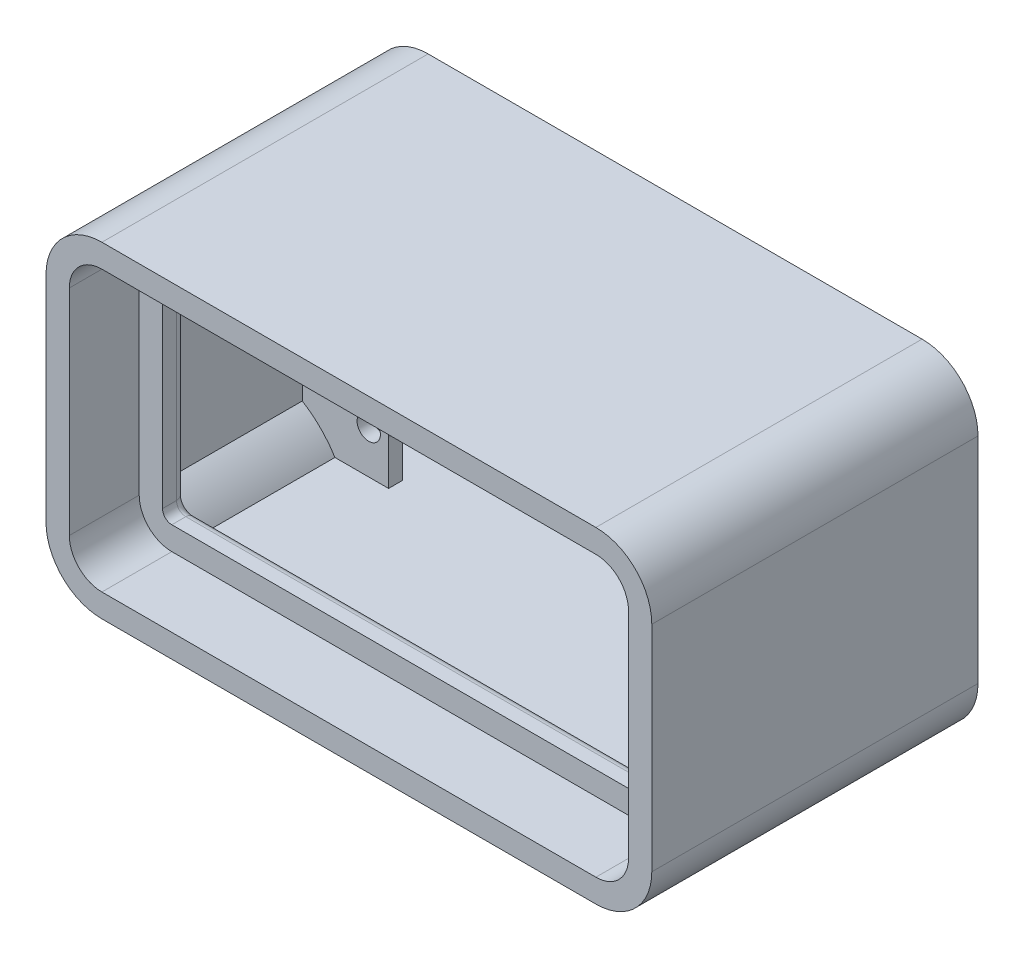
SolidWorks part; units mm, degrees
ref_plane "Спереди" through (0, 0, 0) normal (0, 0, 1) x (1, 0, 0)
ref_plane "Сверху" through (0, 0, 0) normal (0, 1, 0) x (1, 0, 0)
ref_plane "Справа" through (0, 0, 0) normal (1, 0, 0) x (0, 0, -1)
sketch "Эскиз1" plane through (0, 0, 0) normal (0, 0, 1) x (1, 0, 0)
  line L1 (-53, 35) -> (53, 35)
  line L2 (-65, 23) -> (-65, -23)
  line L3 (-53, -35) -> (53, -35)
  line L4 (65, 23) -> (65, -23)
  line L5 (-65, 35) -> (65, -35) construction
  line L6 (-65, -35) -> (65, 35) construction
  arc A0 (-65, -23) -> (-53, -35) centre (-53, -23) ccw
  arc A1 (53, -35) -> (65, -23) centre (53, -23) ccw
  arc A2 (53, 35) -> (65, 23) centre (53, 23) cw
  arc A3 (-53, 35) -> (-65, 23) centre (-53, 23) ccw
  point P0 (0, 0)
  dimension "D3" = 12
  dimension "D1" = 130
  dimension "D2" = 70
extrude "Бобышка-Вытянуть1" add sketch "Эскиз1" along normal blind 70
sketch "Эскиз2" plane through (0, 0, 70) normal (0, 0, 1) x (1, 0, 0)
  line L8 (-53, -30) -> (53, -30)
  line L9 (60, -23) -> (60, 23)
  line L10 (53, 30) -> (-53, 30)
  line L11 (-60, 23) -> (-60, -23)
  line L12 (-53, -30) -> (53, -30)
  line L13 (60, -23) -> (60, 23)
  line L14 (53, 30) -> (-53, 30)
  line L15 (-60, 23) -> (-60, -23)
  arc A8 (-60, -23) -> (-53, -30) centre (-53, -23) ccw
  arc A9 (53, -30) -> (60, -23) centre (53, -23) ccw
  arc A10 (60, 23) -> (53, 30) centre (53, 23) ccw
  arc A11 (-53, 30) -> (-60, 23) centre (-53, 23) ccw
  arc A12 (-60, -23) -> (-53, -30) centre (-53, -23) ccw
  arc A13 (53, -30) -> (60, -23) centre (53, -23) ccw
  arc A14 (60, 23) -> (53, 30) centre (53, 23) ccw
  arc A15 (-53, 30) -> (-60, 23) centre (-53, 23) ccw
  dimension "D1" = 5
extrude "Вырез-Вытянуть1" cut sketch "Эскиз2" against normal blind 70
sketch "Эскиз3" plane through (0, 0, 70) normal (0, 0, 1) x (1, 0, 0)
  line L16 (-53, -25) -> (53, -25)
  line L17 (55, -23) -> (55, 23)
  line L18 (53, 25) -> (-53, 25)
  line L19 (-55, 23) -> (-55, -23)
  line L20 (-53, -25) -> (53, -25)
  line L21 (55, -23) -> (55, 23)
  line L22 (53, 25) -> (-53, 25)
  line L23 (-55, 23) -> (-55, -23)
  line L28 (-53, -30) -> (53, -30)
  line L29 (60, -23) -> (60, 23)
  line L30 (53, 30) -> (-53, 30)
  line L31 (-60, 23) -> (-60, -23)
  line L32 (-53, -30) -> (53, -30)
  line L33 (60, -23) -> (60, 23)
  line L34 (53, 30) -> (-53, 30)
  line L35 (-60, 23) -> (-60, -23)
  arc A16 (53, -25) -> (55, -23) centre (53, -23) ccw
  arc A17 (-55, -23) -> (-53, -25) centre (-53, -23) ccw
  arc A18 (55, 23) -> (53, 25) centre (53, 23) ccw
  arc A19 (-53, 25) -> (-55, 23) centre (-53, 23) ccw
  arc A20 (53, -25) -> (55, -23) centre (53, -23) ccw
  arc A21 (-55, -23) -> (-53, -25) centre (-53, -23) ccw
  arc A22 (55, 23) -> (53, 25) centre (53, 23) ccw
  arc A23 (-53, 25) -> (-55, 23) centre (-53, 23) ccw
  arc A28 (-60, -23) -> (-53, -30) centre (-53, -23) ccw
  arc A29 (53, -30) -> (60, -23) centre (53, -23) ccw
  arc A30 (60, 23) -> (53, 30) centre (53, 23) ccw
  arc A31 (-53, 30) -> (-60, 23) centre (-53, 23) ccw
  arc A32 (-60, -23) -> (-53, -30) centre (-53, -23) ccw
  arc A33 (53, -30) -> (60, -23) centre (53, -23) ccw
  arc A34 (60, 23) -> (53, 30) centre (53, 23) ccw
  arc A35 (-53, 30) -> (-60, 23) centre (-53, 23) ccw
  dimension "D1" = 5
  dimension "D2" = 5
extrude "Бобышка-Вытянуть2" add sketch "Эскиз3" against normal blind 20
extrude "Вырез-Вытянуть2" cut sketch "Эскиз3<2>" against normal blind 15
sketch "Эскиз3<2>" plane through (0, 0, 70) normal (0, 0, 1) x (1, 0, 0) same geometry as "Эскиз3"
sketch "Эскиз4" plane through (0, 0, 50) normal (0, 0, -1) x (-1, 0, 0)
  line L0 (0, 0) -> (0, 10.1301) construction
  line L1 (0, 0) -> (-7.0526, 0) construction
  arc A0 (-53, 30) -> (-60, 23) centre (-71.0034, 41.0034) cw
  arc A1 (-53, 30) -> (-60, 23) centre (-53, 23) ccw construction
  arc A2 (-53, 30) -> (-60, 23) centre (-53, 23) ccw
  arc A3 (53, 30) -> (60, 23) centre (71.0034, 41.0034) ccw
  arc A4 (53, 30) -> (60, 23) centre (53, 23) cw
  arc A5 (53, -30) -> (60, -23) centre (53, -23) ccw
  arc A6 (53, -30) -> (60, -23) centre (71.0034, -41.0034) cw
  arc A7 (-53, -30) -> (-60, -23) centre (-71.0034, -41.0034) ccw
  arc A8 (-53, -30) -> (-60, -23) centre (-53, -23) cw
extrude "Бобышка-Вытянуть3" add sketch "Эскиз4" along normal blind 50
sketch "Эскиз5" plane through (0, 0, 0) normal (0, 0, -1) x (-1, 0, 0)
  line L0 (0, 0) -> (0, 12.862) construction
  line L1 (0, 0) -> (-14.0048, 0) construction
  circle A0 centre (-58.8652, 28.3549) radius 1.45
  circle A1 centre (58.8652, 28.3549) radius 1.45
  circle A2 centre (58.8652, -28.3549) radius 1.45
  circle A3 centre (-58.8652, -28.3549) radius 1.45
  dimension "D1" = 2.9
extrude "Вырез-Вытянуть3" cut sketch "Эскиз5" against normal blind 15
fillet "Скругление1" radius 2 8 edges at (54.4142, -24.4142, 50) (0, -25, 50) (-54.4142, -24.4142, 50) (-55, 0, 50) (-54.4142, 24.4142, 50) (0, 25, 50) (54.4142, 24.4142, 50) (55, 0, 50)
ref_plane "Плоскость1" through (0, 0, 20) normal (0, 0, -1) x (-1, 0, 0)
sketch "Эскиз6" plane through (0, 0, 20) normal (0, 0, -1) x (-1, 0, 0)
  line L0 (0, 0) -> (0, 11.0794) construction
  line L1 (61.4853, 31.4853) -> (41.4853, 31.4853)
  line L2 (61.4853, 31.4853) -> (61.4853, 15.4853)
  line L3 (61.4853, 15.4853) -> (46.4853, 15.4853)
  line L4 (41.4853, 31.4853) -> (41.4853, 20.4853)
  line L5 (0, 0) -> (9.5492, 0) construction
  line L6 (-61.4853, 15.4853) -> (-46.4853, 15.4853)
  line L7 (-41.4853, 31.4853) -> (-41.4853, 20.4853)
  line L8 (-61.4853, 31.4853) -> (-41.4853, 31.4853)
  line L9 (-61.4853, 31.4853) -> (-61.4853, 15.4853)
  line L10 (-61.4853, -31.4853) -> (-61.4853, -15.4853)
  line L11 (-61.4853, -31.4853) -> (-41.4853, -31.4853)
  line L12 (-41.4853, -31.4853) -> (-41.4853, -20.4853)
  line L13 (-61.4853, -15.4853) -> (-46.4853, -15.4853)
  line L14 (61.4853, -15.4853) -> (46.4853, -15.4853)
  line L15 (41.4853, -31.4853) -> (41.4853, -20.4853)
  line L16 (61.4853, -31.4853) -> (41.4853, -31.4853)
  line L17 (61.4853, -31.4853) -> (61.4853, -15.4853)
  arc A0 (65, 23) -> (53, 35) centre (53, 23) ccw construction
  arc A1 (46.4853, 15.4853) -> (41.4853, 20.4853) centre (46.4853, 20.4853) cw
  arc A2 (-46.4853, 15.4853) -> (-41.4853, 20.4853) centre (-46.4853, 20.4853) ccw
  arc A3 (-46.4853, -15.4853) -> (-41.4853, -20.4853) centre (-46.4853, -20.4853) cw
  arc A4 (46.4853, -15.4853) -> (41.4853, -20.4853) centre (46.4853, -20.4853) ccw
  dimension "D1" = 5
  dimension "D2" = 20
  dimension "D3" = 16
extrude "Бобышка-Вытянуть4" add sketch "Эскиз6" along normal blind 3
sketch "Эскиз7" plane through (0, 0, 17) normal (0, 0, -1) x (-1, 0, 0)
  line L0 (0, 0) -> (0, 11.8557) construction
  line L1 (0, 0) -> (8.1095, 0) construction
  circle A0 centre (-46.0541, 20.9358) radius 2.5
  circle A1 centre (45.7459, 20.9358) radius 2.5
  circle A2 centre (45.7459, -20.8642) radius 2.5
  circle A3 centre (-46.0541, -20.8642) radius 2.5
  dimension "D1" = 5
  dimension "D2" = 5
  dimension "D3" = 5
  dimension "D4" = 5
extrude "Вырез-Вытянуть4" cut sketch "Эскиз7" against normal blind 4
